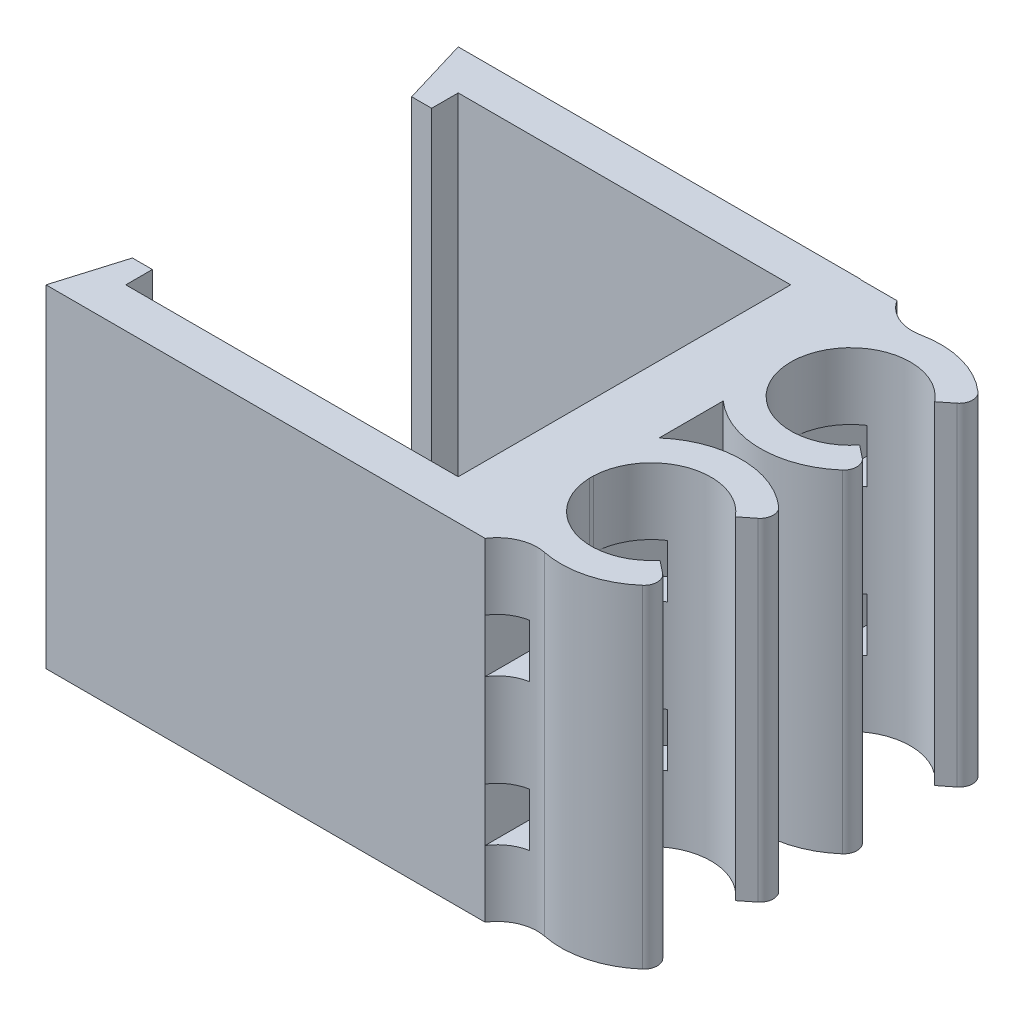
SolidWorks part; units mm, degrees
ref_plane "Спереди" through (0, 0, 0) normal (0, 0, 1) x (1, 0, 0)
ref_plane "Сверху" through (0, 0, 0) normal (0, 1, 0) x (1, 0, 0)
ref_plane "Справа" through (0, 0, 0) normal (1, 0, 0) x (0, 0, -1)
sketch "Эскиз1" plane through (0, 0, 0) normal (0, 1, 0) x (1, 0, 0)
  line L0 (-66.8258, 34.9697) -> (-66.8258, 29.9697)
  line L1 (-63.8258, 29.9697) -> (-63.8258, 31.9697)
  line L2 (-63.8258, 31.9697) -> (-38.8258, 31.9697)
  line L3 (-38.8258, 31.9697) -> (-38.8258, 6.9697)
  line L4 (-38.8258, 6.9697) -> (-63.8258, 6.9697)
  line L5 (-63.8258, 6.9697) -> (-63.8258, 8.9697)
  line L6 (-63.8258, 8.9697) -> (-66.8258, 8.9697)
  line L7 (-66.8258, 8.9697) -> (-66.8258, 3.9697)
  line L8 (-66.8258, 3.9697) -> (-22.1235, 3.9697)
  line L9 (-22.1235, 3.9697) -> (-36.579, 34.9697)
  line L10 (-36.579, 34.9697) -> (-66.8258, 34.9697)
  line L11 (-66.8258, 29.9697) -> (-63.8258, 29.9697)
  dimension "D1" = 25
  dimension "D2" = 25
  dimension "D3" = 25
  dimension "D4" = 155
  dimension "D5" = 3
  dimension "D6" = 3
  dimension "D7" = 3
  dimension "D8" = 3
  dimension "D9" = 2
  dimension "D10" = 2
extrude "Бобышка-Вытянуть1" add sketch "Эскиз1" along normal blind 25
sketch "Эскиз3" plane through (0, 0, 0) normal (0, -1, 0) x (1, 0, 0)
  line L0 (-66.8258, -3.9697) -> (-65.3258, -8.9697)
  line L1 (-63.8258, -8.9697) -> (-66.8258, -8.9697) construction
  line L2 (-65.3258, -8.9697) -> (-66.8258, -8.9697)
  line L3 (-66.8258, -8.9697) -> (-66.8258, -3.9697)
  line L4 (-66.8258, -29.9697) -> (-66.8258, -34.9697)
  line L5 (-66.8258, -34.9697) -> (-65.3258, -29.9697)
  line L6 (-66.8258, -29.9697) -> (-63.8258, -29.9697) construction
  line L7 (-65.3258, -29.9697) -> (-66.8258, -29.9697)
extrude "Вырез-Вытянуть4" cut sketch "Эскиз3" against normal through all
sketch "Эскиз7" plane through (0, 0, 0) normal (0, -1, 0) x (-1, 0, 0)
  line L1 (36.0076, 1.3029) -> (19.3993, 1.3029)
  line L2 (36.0076, 1.3029) -> (36.0076, 39.7765)
  line L3 (36.0076, 39.7765) -> (19.3993, 39.7765)
  line L4 (19.3993, 1.3029) -> (19.3993, 39.7765)
extrude "Вырез-Вытянуть14" cut sketch "Эскиз7" against normal through all
sketch "Эскиз8" plane through (0, 0, 0) normal (0, -1, 0) x (-1, 0, 0)
  line L0 (66.8258, 3.9697) -> (36.0076, 3.9697) construction
  line L1 (38.7989, 3.9697) -> (33.7989, 3.9697)
  line L2 (38.7989, 3.9697) -> (38.7989, 34.9383)
  line L3 (38.7989, 34.9383) -> (33.7989, 34.9383)
  line L4 (33.7989, 3.9697) -> (33.7989, 34.9383)
  dimension "D1" = 5
extrude "Бобышка-Вытянуть2" add sketch "Эскиз8" against normal up to surface (25 mm away) up to face at (-54.2963, 25, -20.5678)
sketch "Эскиз9" plane through (0, 0, 0) normal (0, -1, 0) x (1, 0, 0)
  line L0 (-33.7989, -19.454) -> (1.2661, -19.454) construction
  line L1 (-33.7989, -34.9383) -> (-33.7989, -3.9697) construction
  line L2 (-33.7989, -11.954) -> (-5.8657, -11.954) construction
  line L3 (-33.7989, -26.954) -> (-9.7824, -26.954) construction
  line L4 (-29.2989, -3.3613) -> (-29.2989, -35.1038) construction
  line L5 (-25.7989, -3.3613) -> (-25.7989, -35.1038) construction
  line L6 (-24.0009, -3.3613) -> (-24.0009, -34.4935) construction
  line L7 (-25.7989, -9.1217) -> (-24.0009, -7.6955)
  line L8 (-25.7989, -14.7863) -> (-24.0009, -16.2125)
  line L9 (-25.7989, -24.1307) -> (-24.0009, -22.7126)
  line L10 (-25.7989, -29.7773) -> (-24.0009, -31.1954)
  arc A0 (-25.7989, -9.1217) -> (-25.7989, -14.7863) centre (-29.2989, -11.954) ccw
  arc A1 (-25.7989, -24.1307) -> (-25.7989, -29.7773) centre (-29.2989, -26.954) ccw
  arc A2 (-24.0009, -7.6955) -> (-24.0009, -16.2125) centre (-29.2989, -11.954) ccw
  arc A3 (-24.0009, -22.7126) -> (-24.0009, -31.1954) centre (-29.2989, -26.954) ccw
  dimension "D1" = 7.5
  dimension "D2" = 7.5
  dimension "D3" = 4.5
  dimension "D4" = 3.5
extrude "Бобышка-Вытянуть3" add sketch "Эскиз9" against normal up to surface (25 mm away) up to face at (-52.7142, 25, -21.6795)
fillet "Скругление2" radius 3 2 edges at (-33.7989, 12.5, -6.8594) (-33.7989, 12.5, -32.0343)
fillet "Скругление4" radius 1 4 edges at (-24.0009, 12.5, -7.6955) (-24.0009, 12.5, -16.2125) (-24.0009, 12.5, -31.1954) (-24.0009, 12.5, -22.7126)
sketch "Эскиз10" plane through (0, 0, -3.9697) normal (0, 0, 1) x (1, 0, 0)
  line L0 (-33.7989, 25) -> (-33.7989, 0) construction
  line L1 (-33.7989, 20) -> (-31.7989, 20)
  line L2 (-33.7989, 20) -> (-33.7989, 16)
  line L3 (-33.7989, 16) -> (-31.7989, 16)
  line L4 (-31.7989, 20) -> (-31.7989, 16)
  line L5 (-66.8258, 25) -> (-33.7989, 25) construction
  line L6 (-33.7989, 9) -> (-31.7989, 9)
  line L7 (-33.7989, 9) -> (-33.7989, 5)
  line L8 (-33.7989, 5) -> (-31.7989, 5)
  line L9 (-31.7989, 9) -> (-31.7989, 5)
  line L10 (-66.8258, 0) -> (-33.7989, 0) construction
  dimension "D1" = 2
  dimension "D2" = 2
  dimension "D3" = 4
  dimension "D4" = 4
  dimension "D5" = 5
  dimension "D6" = 5
extrude "Вырез-Вытянуть15" cut sketch "Эскиз10" against normal through all
